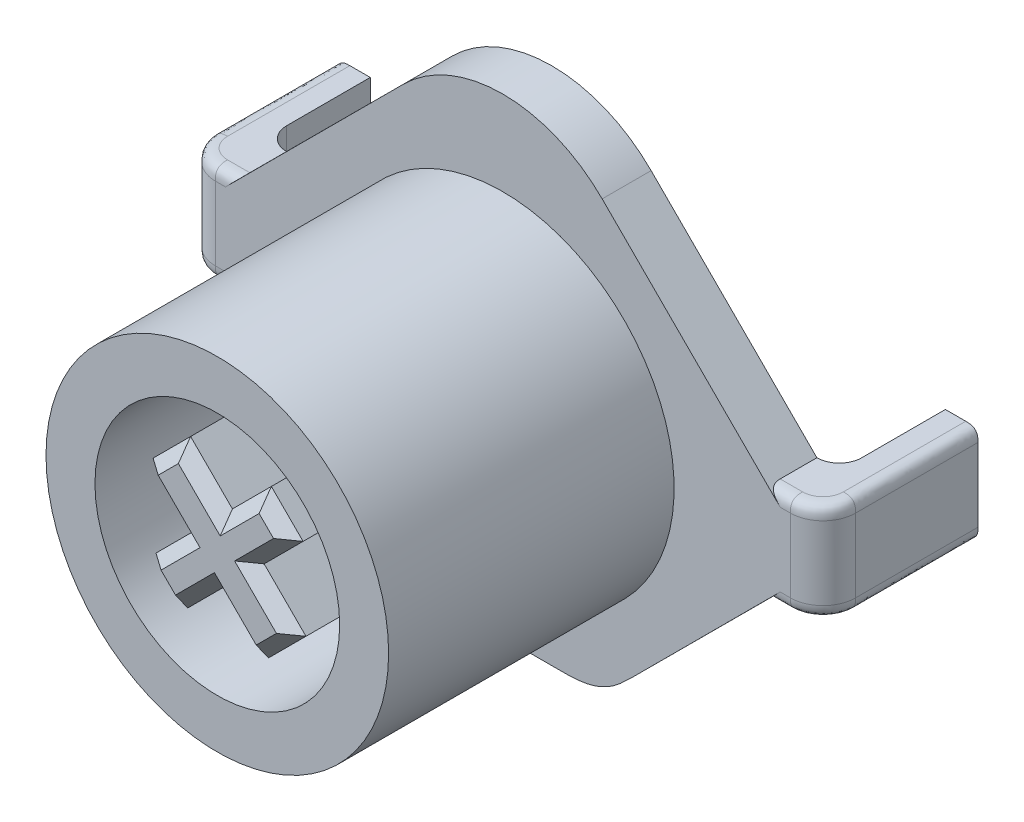
SolidWorks part; units mm, degrees
ref_plane "Front Plane" through (0, 0, 0) normal (0, 0, 1) x (1, 0, 0)
ref_plane "Top Plane" through (0, 0, 0) normal (0, 1, 0) x (1, 0, 0)
ref_plane "Right Plane" through (0, 0, 0) normal (1, 0, 0) x (0, 0, -1)
sketch "Cherry" plane through (0, 0, 0) normal (0, 0, 1) x (1, 0, 0)
  line L0 (0, -1000) -> (0, 49000) construction
  line L1 (-1000, 0) -> (49000, 0) construction
  line L2 (1.0253, 1.8031) -> (1.8031, 1.0253)
  line L3 (1.0253, 1.8031) -> (-1.8031, -1.0253)
  line L4 (1.8031, 1.0253) -> (-1.0253, -1.8031)
  line L5 (-1.8031, -1.0253) -> (-1.0253, -1.8031)
  line L6 (1.0253, 1.8031) -> (-1.0253, -1.8031) construction
  line L7 (1.8031, 1.0253) -> (-1.8031, -1.0253) construction
  line L8 (0.9546, -1.8738) -> (-1.8738, 0.9546)
  line L9 (0.9546, -1.8738) -> (1.8738, -0.9546)
  line L10 (-1.8738, 0.9546) -> (-0.9546, 1.8738)
  line L11 (1.8738, -0.9546) -> (-0.9546, 1.8738)
  line L12 (0.9546, -1.8738) -> (-0.9546, 1.8738) construction
  line L13 (-1.8738, 0.9546) -> (1.8738, -0.9546) construction
  circle A0 centre (0, 0) radius 4.2
  circle A1 centre (0, 0) radius 3
  dimension "D1" = 8.4
  dimension "D2" = 6
  dimension "D3" = 1.1
  dimension "D4" = 4
  dimension "D5" = 45
  dimension "D6" = 4
  dimension "D7" = 1.3
  dimension "D8" = 45
extrude "Outer Cylinder" add sketch "Cherry" along normal blind 7 contours L4 L11 L3 L8 | L9 L11 L4 L8 | L4 L8 L3 L5 | L3 L11 L10 L8 | L11 L4 L2 L3 | A0 A1 region at (0.9369, 0.9369, 0) region at (0, 0, 0) region at (-0.9016, 0.9016, 0) region at (0.9016, -0.9016, 0) region at (-0.9369, -0.9369, 0) region at (-4.0812, 0, 0)
sketch "Inner Gap" plane through (0, 0, 0) normal (0, 0, 1) x (1, 0, 0)
  line L0 (-1000, 0) -> (49000, 0) construction
  line L1 (0, -1000) -> (0, 49000) construction
  circle A0 centre (0, 0) radius 3
  dimension "D1" = 6
sketch "Base Shape" plane through (0, 0, 0) normal (0, 0, 1) x (1, 0, 0)
  line L5 (0, 0) -> (50000, 0) construction
  line L6 (0, -1000) -> (0, 49000) construction
  line L7 (-7.85, 0) -> (-7.85, -50000) construction
  line L8 (7.85, 0) -> (7.85, -50000) construction
  line L9 (-1000, 1.2) -> (49000, 1.2) construction
  line L10 (-1000, -1.2) -> (49000, -1.2) construction
  line L12 (-6.5, -1000) -> (-6.5, 49000) construction
  line L14 (6.5, -1000) -> (6.5, 49000) construction
  line L21 (-713.6068, -705.9068) -> (34641.7323, 34649.4323) construction
  line L22 (-700.6068, -708.3068) -> (34654.7323, 34647.0323) construction
  line L24 (-713.6068, 705.9068) -> (34641.7323, -34649.4323) construction
  line L27 (-700.6068, 708.3068) -> (34654.7323, -34647.0323) construction
  line L28 (-6.5, -1.2) -> (-6.5, 1.2)
  line L29 (-6.5, 1.2) -> (-2.4358, 5.2642)
  line L35 (2.4358, 5.2642) -> (6.5, 1.2)
  line L36 (6.5, 1.2) -> (6.5, -1.2)
  line L37 (6.5, -1.2) -> (2.4358, -5.2642)
  line L38 (2.4358, -5.2642) -> (-2.4358, -5.2642)
  line L39 (-2.4358, -5.2642) -> (-6.5, -1.2)
  arc A0 (-2.4358, 5.2642) -> (2.4358, 5.2642) centre (0, 2.8284) cw
  dimension "D1" = 7.85
  dimension "D2" = 1.2
  dimension "D3" = 1.35
extrude "Inner Wall" add sketch "Inner Gap" along normal blind 3
extrude "Base" add sketch "Base Shape" against normal blind 1.2
sketch "Stand Shape" plane through (0, 0, 0) normal (0, 1, 0) x (1, 0, 0)
  line L0 (-1000, 0) -> (49000, 0) construction
  line L1 (-1000.3818, 3.8) -> (48999.6182, 3.8) construction
  line L2 (-7.85, -1001.4882) -> (-7.85, 48998.5118) construction
  line L3 (0, -1000) -> (0, 49000) construction
  line L4 (-6.5, -997.4352) -> (-6.5, 49002.5648) construction
  line L5 (6.5, -997.4352) -> (6.5, 49002.5648) construction
  line L6 (7.85, -1001.4882) -> (7.85, 48998.5118) construction
  line L7 (-7.05, -998.4603) -> (-7.05, 49001.5397) construction
  line L8 (6.5, 0) -> (7.05, 0)
  line L9 (6.5, 1.2) -> (6.5, 0)
  line L10 (-1021.5655, 1.2) -> (48978.4345, 1.2) construction
  line L11 (-7.85, 3.8) -> (-7.05, 3.8)
  line L12 (-7.05, 3.8) -> (-7.05, 1.75)
  line L13 (7.05, 3.8) -> (7.05, 1.75)
  line L14 (-6.5, 1.2) -> (-6.5, 0)
  line L15 (-6.5, 0) -> (-7.05, 0)
  line L16 (7.85, 3.8) -> (7.05, 3.8)
  line L17 (-7.85, 3.8) -> (-7.85, 0.8)
  line L18 (7.85, 3.8) -> (7.85, 0.8)
  arc A0 (-7.85, 0.8) -> (-7.05, 0) centre (-7.05, 0.8) ccw
  arc A1 (-7.05, 1.75) -> (-6.5, 1.2) centre (-6.5, 1.75) ccw
  arc A2 (7.85, 0.8) -> (7.05, 0) centre (7.05, 0.8) cw
  arc A3 (7.05, 1.75) -> (6.5, 1.2) centre (6.5, 1.75) cw
  dimension "D1" = 3.8
  dimension "D2" = 7.85
  dimension "D3" = 1.35
  dimension "D4" = 0.8
  dimension "D6" = 1.2
extrude "Stand" add sketch "Stand Shape" along normal mid plane 2.4
fillet "Fillet1" radius 2.5 2 edges at (2.4358, -5.2642, -0.6) (-2.4358, -5.2642, -0.6) curvature continuous yes
fillet "Fillet3" radius 0.3 12 edges at (-6.775, -1.2, 0) (-7.6157, -1.2, -0.2343) (-6.775, 1.2, 0) (-7.6157, 1.2, -0.2343) (6.775, -1.2, 0) (7.6157, -1.2, -0.2343) (6.775, 1.2, 0) (7.6157, 1.2, -0.2343) (-7.85, -1.2, -2.3) (-7.85, 1.2, -2.3) (7.85, -1.2, -2.3) (7.85, 1.2, -2.3) curvature continuous yes
sketch "Sketch1" plane through (0, 0, 0) normal (0, 0, 1) x (1, 0, 0)
  line L0 (0, -1000) -> (0, 49000) construction
  line L1 (-1000, 0) -> (49000, 0) construction
  line L2 (-0.9546, 1.8738) -> (0.0707, 0.8485)
  line L3 (-0.9546, 1.8738) -> (-0.0061, 2.8224)
  line L4 (0.0707, 0.8485) -> (1.0193, 1.7971)
  line L5 (-0.0061, 2.8224) -> (1.0193, 1.7971)
  line L6 (1.8031, 1.0253) -> (0.8485, 0.0707)
  line L7 (1.8031, 1.0253) -> (2.8187, 0.0097)
  line L8 (0.8485, 0.0707) -> (1.8641, -0.9449)
  line L9 (2.8187, 0.0097) -> (1.8641, -0.9449)
  line L10 (0.9546, -1.8738) -> (-0.0707, -0.8485)
  line L11 (0.9546, -1.8738) -> (-0.0072, -2.8356)
  line L12 (-0.0707, -0.8485) -> (-1.0325, -1.8103)
  line L13 (-0.0072, -2.8356) -> (-1.0325, -1.8103)
  line L14 (-1.8031, -1.0253) -> (-0.8485, -0.0707)
  line L15 (-1.8031, -1.0253) -> (-2.8203, -0.0081)
  line L16 (-0.8485, -0.0707) -> (-1.8657, 0.9465)
  line L17 (-2.8203, -0.0081) -> (-1.8657, 0.9465)
extrude "Cut-Extrude1" cut sketch "Sketch1" against normal through all both and the other way through all
chamfer "Chamfer1" distance 0.3 angle 45 12 edges at (-0.548, -1.3258, 7) (-1.4142, -1.4142, 7) (-1.3258, -0.548, 7) (-1.3612, 0.4419, 7) (-1.4142, 1.4142, 7) (-0.4419, 1.3612, 7) (0.548, 1.3258, 7) (1.4142, 1.4142, 7) (1.3258, 0.548, 7) (1.3612, -0.4419, 7) (1.4142, -1.4142, 7) (0.4419, -1.3612, 7)
equation "\"Cherry Outter Diameter\" = 8.4"
equation "\"Cherry Inner Diameter\"= 6"
equation "\"Cherry Horizontal Bar Width\"= 1.3"
equation "\"Cherry Horizontal Bar Length\"=4"
equation "\"Cherry Veritcal Bar Width\"=1.1"
equation "\"Cherry Vertical Bar Length\"=4"
equation "\"Cherry Cylinder Height\"= 7"
equation "\"Cherry Inner Wall Height\"= 3"
equation "\"D1@Cherry\"=\"Cherry Outter Diameter\""
equation "\"D3@Cherry\"=\"Cherry Veritcal Bar Width\""
equation "\"D4@Cherry\"=\"Cherry Vertical Bar Length\""
equation "\"D6@Cherry\"=\"Cherry Horizontal Bar Length\""
equation "\"D7@Cherry\"=\"Cherry Horizontal Bar Width\""
equation "\"D1@Inner Gap\"=\"Cherry Inner Diameter\""
